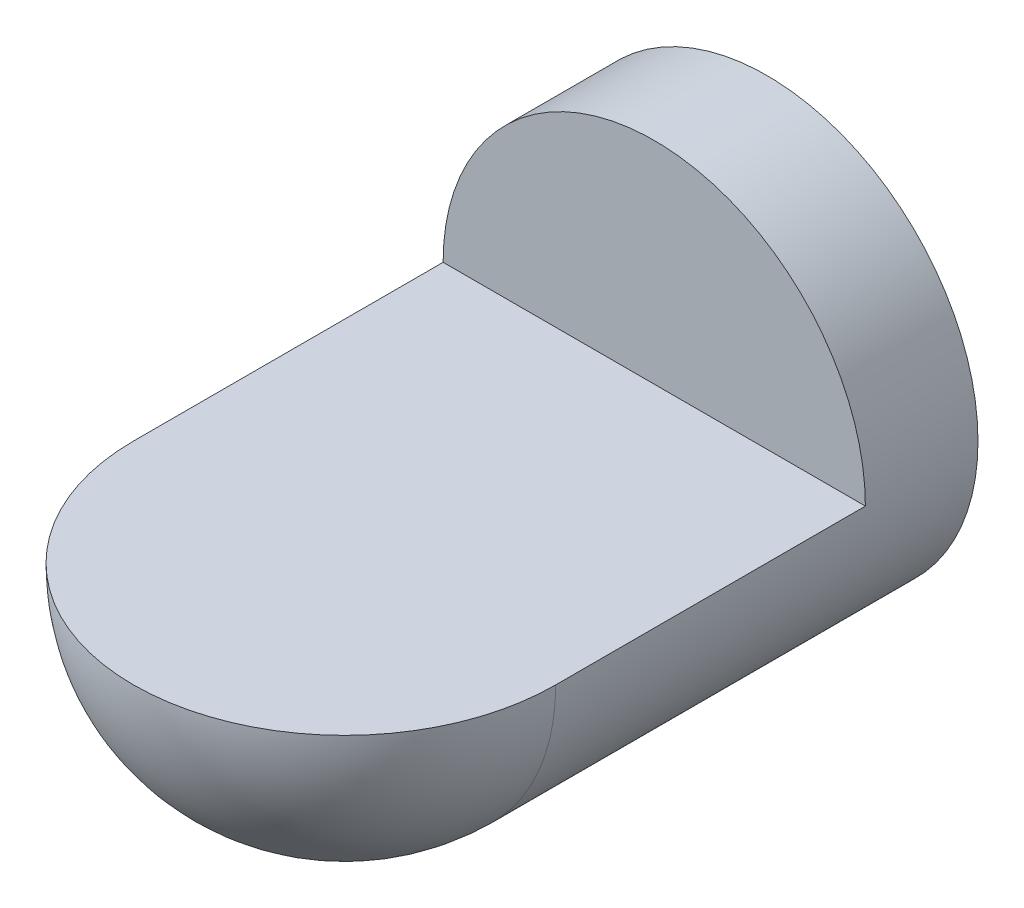
SolidWorks part; units mm, degrees
ref_plane "Front Plane" through (0, 0, 0) normal (0, 0, 1) x (1, 0, 0)
ref_plane "Top Plane" through (0, 0, 0) normal (0, 1, 0) x (1, 0, 0)
ref_plane "Right Plane" through (0, 0, 0) normal (1, 0, 0) x (0, 0, -1)
sketch "Sketch1" plane through (0, 0, 0) normal (1, 0, 0) x (0, 0, -1)
  line L0 (-146.9091, 0) -> (313.5945, 0) construction
  line L1 (150, 0) -> (-75, 0)
  line L2 (150, 0) -> (150, 75)
  line L3 (0, 75) -> (150, 75)
  arc A0 (-75, 0) -> (0, 75) centre (0, 0) cw
  dimension "D1" = 75
  dimension "D2" = 150
revolve "Revolve1" add sketch "Sketch1" angle 360 about L0
sketch "Sketch2" plane through (0, 0, 0) normal (1, 0, 0) x (0, 0, -1)
  line L0 (-88.0407, 0) -> (120.4455, 0) construction
  line L1 (110, 0) -> (110, 75)
  line L2 (150, 75) -> (0, 75) construction
  line L3 (110, 0) -> (-75, 0)
  line L4 (110, 75) -> (0, 75)
  line L5 (150, -75) -> (150, 75) construction
  arc A0 (0, 75) -> (0, -75) centre (0, 0) ccw construction
  arc A1 (-75, 0) -> (0, 75) centre (0, 0) cw
  dimension "D1" = 40
extrude "Cut-Extrude1" cut sketch "Sketch2" along normal through all and the other way through all
ref_axis "Axis1" through (0, 82.5, 0) along (0, -1, 0)
equation "\"link4_diameter\"=150"
equation "\"D1@Sketch1\"=\"link4_diameter\"/2"
equation "\"link4_length\"=150"
equation "\"D2@Sketch1\"=\"link4_length\""
equation "\"base_link_length\"=150"
equation "\"link1_diameter\"=150"
equation "\"link1_length\"=150"
equation "\"link2_diameter\"=150"
equation "\"link2_length\"=300"
equation "\"link3_diameter\"=150"
equation "\"link3_length\"=150"
equation "\"link5_diameter\"=150"
equation "\"link5_length\"=200"
equation "\"end_effector_diameter\"=150"
equation "\"end_effector_length\"=150"
equation "\"base_link_diameterA\"=200"
equation "\"base_link_diameterB\"=150"
equation "\"base_link_lengthA\"=50"
